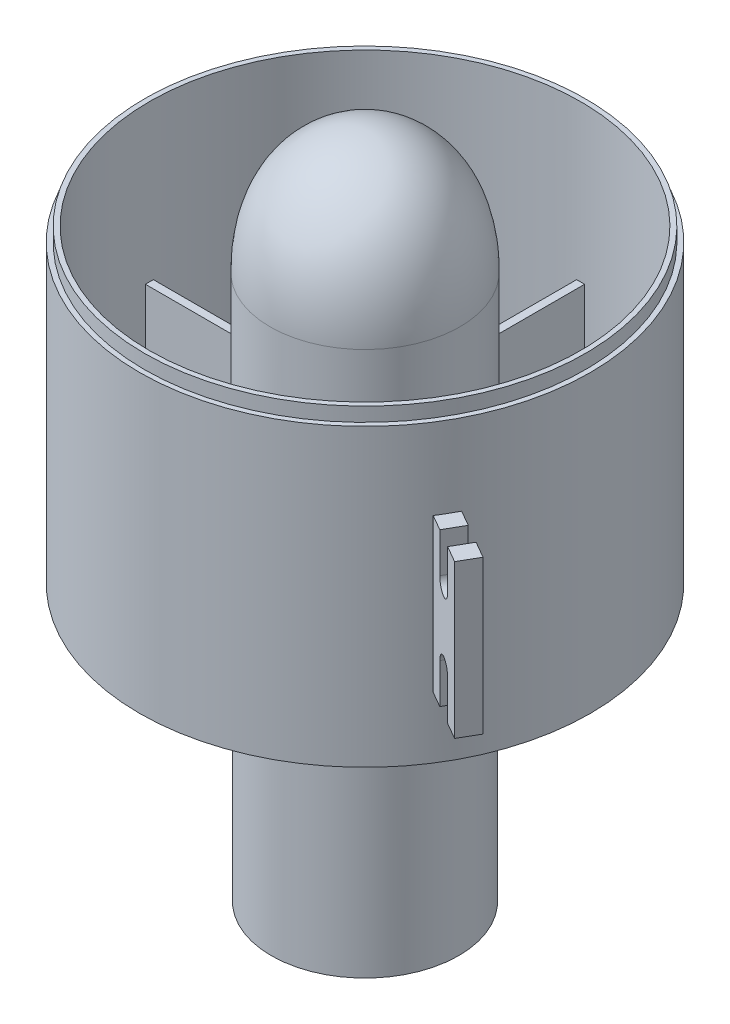
SolidWorks part; units mm, degrees
ref_plane "Front Plane" through (0, 0, 0) normal (0, 0, 1) x (1, 0, 0)
ref_plane "Top Plane" through (0, 0, 0) normal (0, 1, 0) x (1, 0, 0)
ref_plane "Right Plane" through (0, 0, 0) normal (1, 0, 0) x (0, 0, -1)
sketch "Sketch1" plane through (0, 0, 0) normal (0, 1, 0) x (1, 0, 0)
  circle A0 centre (0, 0) radius 36.8
  circle A2 centre (0, 0) radius 35.2
  dimension "D1" = 73.6
  dimension "D2" = 1.6
extrude "Boss-Extrude1" add sketch "Sketch1" along normal blind 50.5
sketch "Sketch2" plane through (0, 0, 0) normal (0, -1, 0) x (1, 0, 0)
  line L0 (-36.8, 0) -> (-16, 0) construction
  line L1 (15.9868, 0.65) -> (35.194, 0.65)
  line L2 (15.9868, -0.65) -> (35.194, -0.65)
  line L3 (11.764, -10.8447) -> (25.3455, -24.4263)
  line L4 (10.8447, -11.764) -> (24.4263, -25.3455)
  line L5 (0.65, -15.9868) -> (0.65, -35.194)
  line L6 (-0.65, -15.9868) -> (-0.65, -35.194)
  line L7 (-10.8447, -11.764) -> (-24.4263, -25.3455)
  line L8 (-11.764, -10.8447) -> (-25.3455, -24.4263)
  line L9 (-15.9868, -0.65) -> (-35.194, -0.65)
  line L10 (-15.9868, 0.65) -> (-35.194, 0.65)
  line L11 (-11.764, 10.8447) -> (-25.3455, 24.4263)
  line L12 (-10.8447, 11.764) -> (-24.4263, 25.3455)
  line L13 (-0.65, 15.9868) -> (-0.65, 35.194)
  line L14 (0.65, 15.9868) -> (0.65, 35.194)
  line L15 (10.8447, 11.764) -> (24.4263, 25.3455)
  line L16 (11.764, 10.8447) -> (25.3455, 24.4263)
  line L17 (-15, 0) -> (15.7396, 0) construction
  circle A0 centre (0, 0) radius 36.8 construction
  arc A1 (-15.9868, -0.65) -> (-11.764, -10.8447) centre (0, 0) ccw
  circle A2 centre (0, 0) radius 15
  circle A3 centre (0, 0) radius 35.2 construction
  circle A4 centre (0, 0) radius 16 construction
  arc A5 (-11.764, 10.8447) -> (-15.9868, 0.65) centre (0, 0) ccw
  arc A6 (-0.65, 15.9868) -> (-10.8447, 11.764) centre (0, 0) ccw
  arc A7 (10.8447, 11.764) -> (0.65, 15.9868) centre (0, 0) ccw
  arc A8 (15.9868, 0.65) -> (11.764, 10.8447) centre (0, 0) ccw
  arc A9 (11.764, -10.8447) -> (15.9868, -0.65) centre (0, 0) ccw
  arc A10 (0.65, -15.9868) -> (10.8447, -11.764) centre (0, 0) ccw
  arc A11 (-10.8447, -11.764) -> (-0.65, -15.9868) centre (0, 0) ccw
  arc A12 (-35.194, 0.65) -> (-35.194, -0.65) centre (0, 0) ccw
  arc A13 (-24.4263, 25.3455) -> (-25.3455, 24.4263) centre (0, 0) ccw
  arc A14 (0.65, 35.194) -> (-0.65, 35.194) centre (0, 0) ccw
  arc A15 (25.3455, 24.4263) -> (24.4263, 25.3455) centre (0, 0) ccw
  arc A16 (35.194, -0.65) -> (35.194, 0.65) centre (0, 0) ccw
  arc A17 (24.4263, -25.3455) -> (25.3455, -24.4263) centre (0, 0) ccw
  arc A18 (-0.65, -35.194) -> (0.65, -35.194) centre (0, 0) ccw
  arc A19 (-25.3455, -24.4263) -> (-24.4263, -25.3455) centre (0, 0) ccw
  point P46 (0, 0)
  dimension "D1" = 32
  dimension "D3" = 1.3
  dimension "D2" = 1
  dimension "D4" = 8
extrude "Boss-Extrude2" add sketch "Sketch2" against normal blind 25
ref_axis "Axis1" through (0, 25, 0) along (0, -1, 0)
ref_plane "Plane1" through (0, 0, 0) normal (-0.5, 0, 0.866) x (0, -1, 0)
sketch "Sketch3" plane through (0, 0, 0) normal (-0.5, 0, 0.866) x (0, -1, 0)
  line L0 (0, 36.8008) -> (-50.5, 36.8008) construction
  line L1 (0, -36.8) -> (0, 36.8) construction
  line L2 (-50.5, 36.8) -> (-50.5, -36.8) construction
  line L3 (-35, 41.45) -> (-10, 41.45) construction
  line L4 (-35, 36.8008) -> (-10, 36.8008)
  line L5 (-35, 36.8008) -> (-35, 39.7)
  line L6 (-35, 46.3008) -> (-10, 46.3008)
  line L7 (-10, 36.8008) -> (-10, 39.7)
  line L8 (-28.5, 43.2) -> (-35, 43.2)
  line L9 (-28.5, 39.7) -> (-35, 39.7)
  line L10 (-35, 43.2) -> (-35, 46.3008)
  line L11 (-22.5, 46.3008) -> (-22.5, 36.8008) construction
  line L12 (-16.5, 39.7) -> (-10, 39.7)
  line L13 (-16.5, 43.2) -> (-10, 43.2)
  line L14 (-10, 43.2) -> (-10, 46.3008)
  line L15 (-50.5, 0) -> (0, 0) construction
  line L16 (-16.5, -39.7) -> (-10, -39.7)
  line L17 (-16.5, -43.2) -> (-10, -43.2)
  line L18 (-35, -43.2) -> (-35, -46.3008)
  line L19 (-28.5, -43.2) -> (-35, -43.2)
  line L20 (-28.5, -39.7) -> (-35, -39.7)
  line L21 (-35, -36.8008) -> (-35, -39.7)
  line L22 (-35, -36.8008) -> (-10, -36.8008)
  line L23 (-10, -36.8008) -> (-10, -39.7)
  line L24 (-10, -43.2) -> (-10, -46.3008)
  line L25 (-35, -46.3008) -> (-10, -46.3008)
  arc A0 (-28.5, 39.7) -> (-28.5, 43.2) centre (-28.5, 41.45) ccw
  arc A1 (-16.5, 39.7) -> (-16.5, 43.2) centre (-16.5, 41.45) cw
  arc A2 (-28.5, -39.7) -> (-28.5, -43.2) centre (-28.5, -41.45) cw
  arc A3 (-16.5, -39.7) -> (-16.5, -43.2) centre (-16.5, -41.45) ccw
  dimension "D4" = 3.5
  dimension "D1" = 10
  dimension "D2" = 25
  dimension "D3" = 9.5
  dimension "D5" = 6.5
extrude "Boss-Extrude3" add sketch "Sketch3" along normal blind 1.7 and the other way blind 1.7 separate body
sketch "Sketch4" plane through (31.8704, 0, 18.4004) normal (-0.866, 0, -0.5) x (-0.5, 0, 0.866)
  line L1 (-1.7, 35) -> (1.7, 35)
  line L2 (-1.7, 35) -> (-1.7, 10)
  line L3 (-1.7, 10) -> (1.7, 10)
  line L4 (1.7, 35) -> (1.7, 10)
extrude "Boss-Extrude4" add sketch "Sketch4" along normal up to surface (0.0401 mm away) up to face at (0, 50.5, 36.8)
sketch "Sketch5" plane through (0, 50.5, 0) normal (0, 1, 0) x (1, 0, 0)
  circle A0 centre (0, 0) radius 36.8 construction
  circle A1 centre (0, 0) radius 36.8
  circle A2 centre (0, 0) radius 36
  dimension "D1" = 0.8
extrude "Cut-Extrude1" cut sketch "Sketch5" against normal blind 2.3
sketch "Sketch6" plane through (0, 0, 0) normal (0, -1, 0) x (1, 0, 0)
  circle A0 centre (0, 0) radius 15.3
  dimension "D1" = 30.6
extrude "Boss-Extrude5" add sketch "Sketch6" along normal blind 50
chamfer "Chamfer1" distance 5 angle 60 1 edges at (0, -50, -15.3) first distance on face at (0, -50, -15.3)
sketch "Sketch7" plane through (0, 0, 0) normal (0, 1, 0) x (1, 0, 0)
  circle A0 centre (0, 0) radius 15.5
  dimension "D1" = 31
extrude "Boss-Extrude6" add sketch "Sketch7" along normal blind 44
sketch "Sketch8" plane through (0, 0, 0) normal (-0.5, 0, 0.866) x (0, -1, 0)
  line L0 (-44, 0) -> (-83.5149, 0) construction
  line L1 (-44, 15.5) -> (-44, -15.5) construction
  line L2 (-64, 19.8889) -> (-64, -13.7445) construction
  line L3 (-64, -8.4837) -> (-64, 8.4837) construction
  line L4 (-55.1765, 15.5) -> (-32.8235, 15.5) construction
  line L5 (-44, 15.5) -> (-44, 0)
  line L6 (-64, 0) -> (-44, 0)
  spline S0 degree 3 poles (-44, 15.5) (-57.9706, 15.5) (-64, 7.0697) (-64, 0) knots 0 0 0 0 1 1 1 1
  dimension "D1" = 20
revolve "Revolve2" add sketch "Sketch8" angle 360 about axis through (0, 25, 0) along (0, -1, 0)
